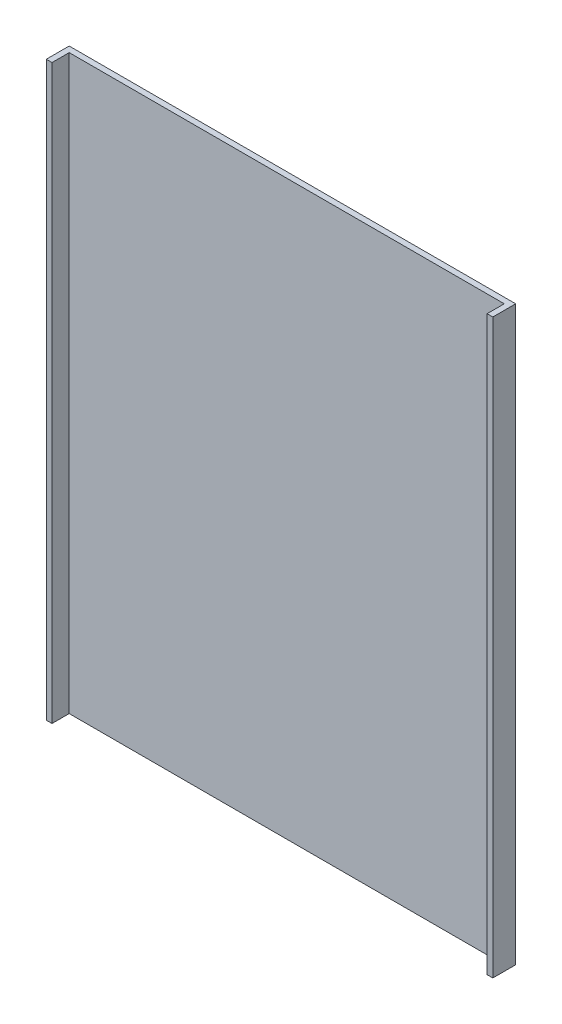
SolidWorks part; units mm, degrees
ref_plane "Ebene vorne" through (0, 0, 0) normal (0, 0, 1) x (1, 0, 0)
ref_plane "Ebene oben" through (0, 0, 0) normal (0, 1, 0) x (1, 0, 0)
ref_plane "Ebene rechts" through (0, 0, 0) normal (1, 0, 0) x (0, 0, -1)
sketch "Skizze1" plane through (0, 0, 0) normal (0, 1, 0) x (1, 0, 0)
  line L0 (0, 0) -> (10, 0)
  line L5 (10, 0) -> (10, 30)
  line L6 (10, 30) -> (770, 30)
  line L7 (770, 30) -> (770, 0)
  line L8 (770, 0) -> (780, 0)
  line L9 (780, 0) -> (780, 40)
  line L10 (780, 40) -> (0, 40)
  line L11 (0, 40) -> (0, 0)
  dimension "D1" = 780
  dimension "D2" = 10
  dimension "D3" = 10
  dimension "D4" = 40
  dimension "D5" = 30
extrude "Aufsatz-Linear austragen1" add sketch "Skizze1" along normal blind 1000
